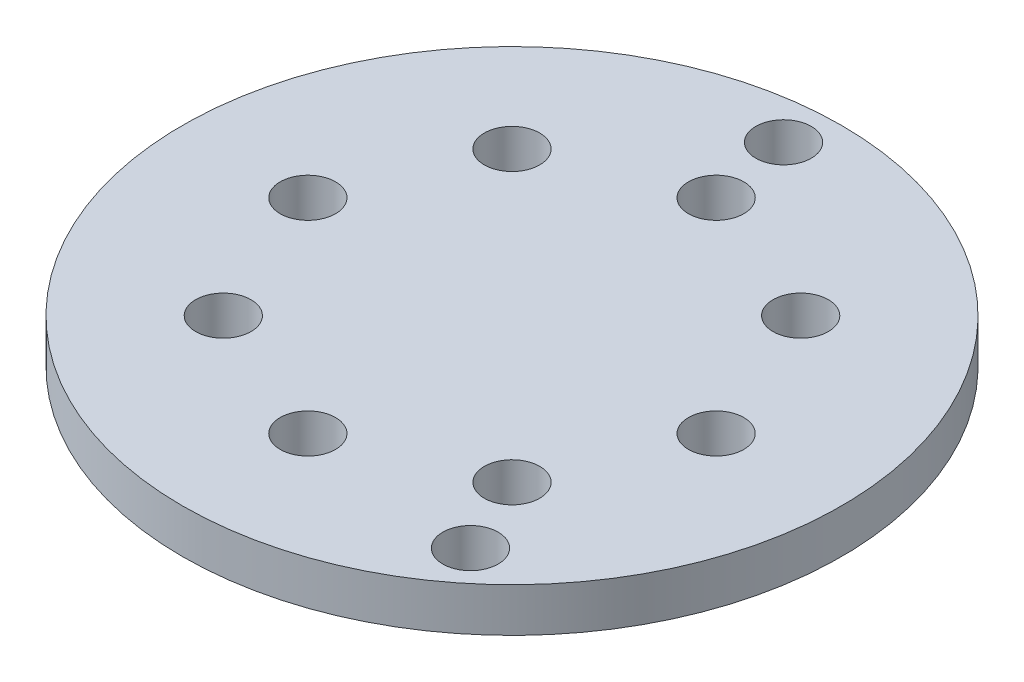
SolidWorks part; units mm, degrees
ref_plane "Front Plane" through (0, 0, 0) normal (0, 0, 1) x (1, 0, 0)
ref_plane "Top Plane" through (0, 0, 0) normal (0, 1, 0) x (1, 0, 0)
ref_plane "Right Plane" through (0, 0, 0) normal (1, 0, 0) x (0, 0, -1)
sketch "Sketch1" plane through (0, 0, 0) normal (0, 1, 0) x (1, 0, 0)
  circle A0 centre (0, 0) radius 47.625
  dimension "D1" = 95.25
extrude "Boss-Extrude2" add sketch "Sketch1" along normal blind 6.35 contours A0
sketch "Sketch3" plane through (0, 6.35, 0) normal (0, 1, 0) x (1, 0, 0)
  circle A0 centre (0, 0) radius 29.5
  dimension "D1" = 59
sketch "Sketch4" plane through (0, 6.35, 0) normal (0, 1, 0) x (1, 0, 0)
  circle A0 centre (-29.5, 0) radius 4
  circle A1 centre (0, 0) radius 29.5 construction
  dimension "D1" = 8
extrude "Cut-Extrude1" cut sketch "Sketch4" against normal through all contours A0
ref_axis "Axis1" through (0, 6.35, 0) along (0, 1, 0)
pattern_circular "CirPattern2" count 8 over 360 about axis through (0, 6.35, 0) along (0, 1, 0) of "Cut-Extrude1"
sketch "Sketch5" plane through (0, 6.35, 0) normal (0, 1, 0) x (1, 0, 0)
  circle A0 centre (0, 0) radius 41.3639
  circle A1 centre (-2.0725, 41.3119) radius 4
  dimension "D1" = 82.7278
  dimension "D2" = 8
extrude "Cut-Extrude2" cut sketch "Sketch5" against normal through all contours A1
sketch "Sketch6" plane through (0, 6.35, 0) normal (0, 1, 0) x (1, 0, 0)
  line L0 (-2.0725, 41.3119) -> (26.0949, -32.0941)
  circle A0 centre (0, 0) radius 41.3639
  circle A1 centre (26.0949, -32.0941) radius 4
  dimension "D2" = 8
  dimension "D1" = 73.406
sketch "Sketch7" plane through (0, 6.35, 0) normal (0, 1, 0) x (1, 0, 0)
extrude "Cut-Extrude4" cut sketch "Sketch6" against normal through all contours A1
